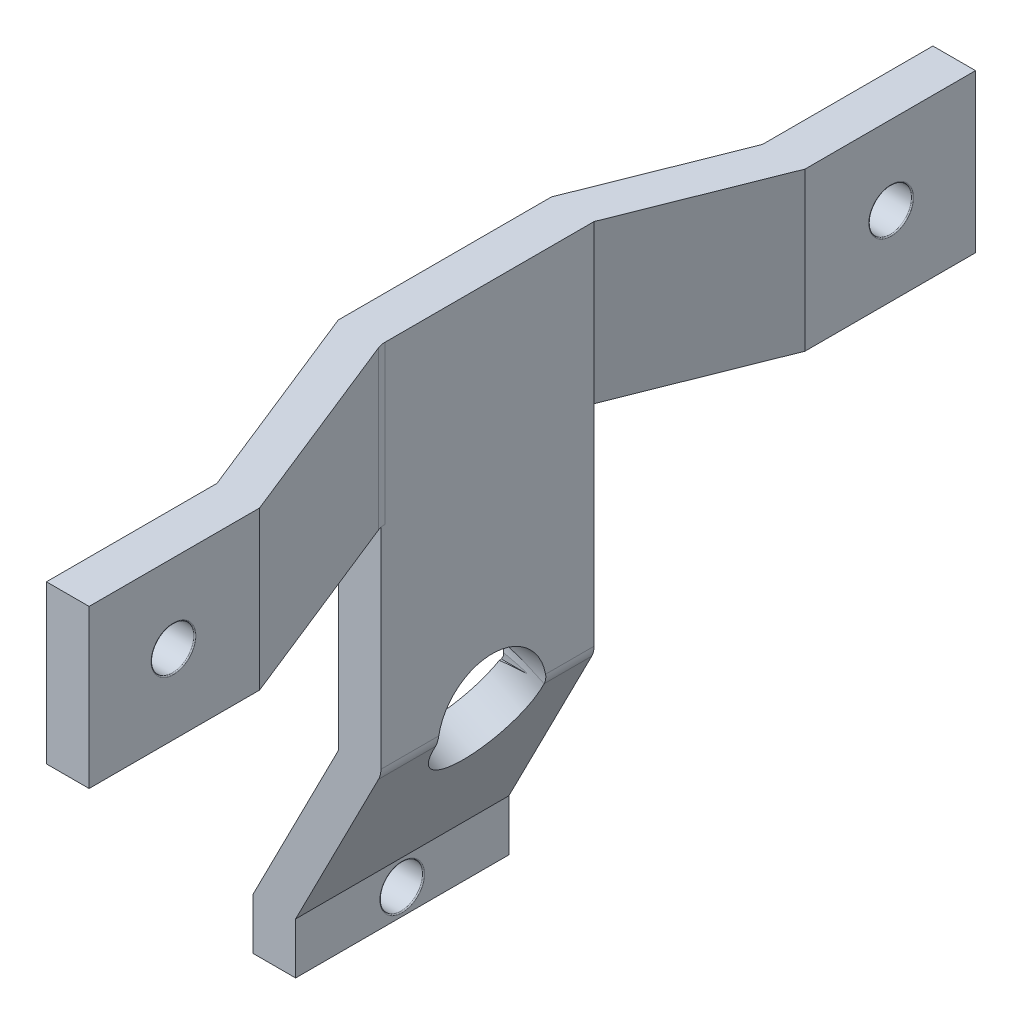
SolidWorks part; units mm, degrees
ref_plane "Front Plane" through (0, 0, 0) normal (0, 0, 1) x (1, 0, 0)
ref_plane "Top Plane" through (0, 0, 0) normal (0, 1, 0) x (1, 0, 0)
ref_plane "Right Plane" through (0, 0, 0) normal (1, 0, 0) x (0, 0, -1)
sketch "Sketch1" plane through (0, 0, 0) normal (0, 0, 1) x (1, 0, 0)
  line L0 (-10, 50.4903) -> (0, 50.4903)
  line L1 (0, 50.4903) -> (0, 0)
  line L2 (0, 0) -> (-20, -39.1735)
  line L3 (-20, -39.1735) -> (-20, -51.1735)
  line L4 (-20, -51.1735) -> (-30, -51.1735)
  line L5 (-30, -51.1735) -> (-30, -39.1735)
  line L6 (-30, -39.1735) -> (-10, 0)
  line L7 (-10, 0) -> (-10, 50.4903)
  line L8 (-30, -39.1735) -> (-30, 70.8733) construction
  line L9 (-10, 50.4903) -> (-30, 50.4903) construction
extrude "Boss-Extrude1" add sketch "Sketch1" along normal blind 50
sketch "Sketch2" plane through (0, 50.4903, 0) normal (0, 1, 0) x (1, 0, 0)
  line L0 (-10, -50) -> (8.9559, -97.4002)
  line L1 (8.9559, -97.4002) -> (8.9559, -137.4002)
  line L2 (8.9559, -137.4002) -> (18.9559, -137.4002)
  line L3 (18.9559, -137.4002) -> (18.9559, -97.4002)
  line L4 (18.9559, -97.4002) -> (0, -50)
  line L5 (0, -50) -> (0, 0)
  line L6 (0, 0) -> (14.0829, 35.4022)
  line L7 (14.0829, 35.4022) -> (14.0829, 75.4022)
  line L8 (14.0829, 75.4022) -> (4.0829, 75.4022)
  line L9 (4.0829, 75.4022) -> (4.0829, 35.4022)
  line L10 (4.0829, 35.4022) -> (-10, 0)
  line L11 (-10, 0) -> (-10, -50)
  line L12 (0, 0) -> (-10, 0) construction
  line L13 (0, -50) -> (-10, -50) construction
extrude "Boss-Extrude2" add sketch "Sketch2" along normal blind 37
fillet "Fillet1" radius 5.08 1 edges at (0, 0, 25)
fillet "Fillet2" radius 5.08 1 edges at (0, 68.9903, 50)
sketch "Sketch3" plane through (-10, 0, 0) normal (-1, 0, 0) x (0, 0, 1)
  circle A1 centre (-55.6073, 68.9903) radius 5
  circle A2 centre (117.6053, 68.9903) radius 5
extrude "Cut-Extrude3" cut sketch "Sketch3" against normal blind 50.8
sketch "Sketch4" plane through (-30, 0, 0) normal (-1, 0, 0) x (0, 0, 1)
  circle A0 centre (25, -45.17) radius 5
extrude "Cut-Extrude4" cut sketch "Sketch4" against normal through all
fillet "Fillet4" radius 0.254 1 edges at (-20, -45.17, 30)
fillet "Fillet5" radius 0.254 1 edges at (-30, -45.17, 30)
fillet "Fillet6" radius 0.254 1 edges at (14.0829, 68.9903, -50.6073)
fillet "Fillet7" radius 0.254 1 edges at (4.0829, 68.9903, -60.6073)
fillet "Fillet8" radius 0.254 1 edges at (18.9559, 68.9903, 122.6053)
fillet "Fillet9" radius 0.254 1 edges at (8.9559, 68.9903, 112.6053)
sketch "Sketch18" plane through (0, 0, 0) normal (0.8906, -0.4547, 0) x (-0.4547, -0.8906, 0)
  line L0 (1.2218, 0) -> (1.2218, -50) construction
  line L1 (1.2218, -11.1587) -> (1.2218, -36.6343)
  arc A0 (1.2218, -11.1587) -> (1.2218, -36.6343) centre (2.1042, -23.8965) cw
extrude "Cut-Extrude10" cut sketch "Sketch18" against normal blind 50.8
sketch "Sketch19" plane through (-10, 0, 0) normal (-1, 0, 0) x (0, 0, 1)
sketch "Sketch20" plane through (0, 0, 0) normal (1, 0, 0) x (0, 0, -1)
  line L0 (-11.1587, -1.0882) -> (-36.6343, -1.0882)
  arc A0 (-36.6343, -1.0882) -> (-11.1587, -1.0882) centre (-23.8965, -1.0882) cw
extrude "Cut-Extrude11" cut sketch "Sketch20" against normal blind 50.8
